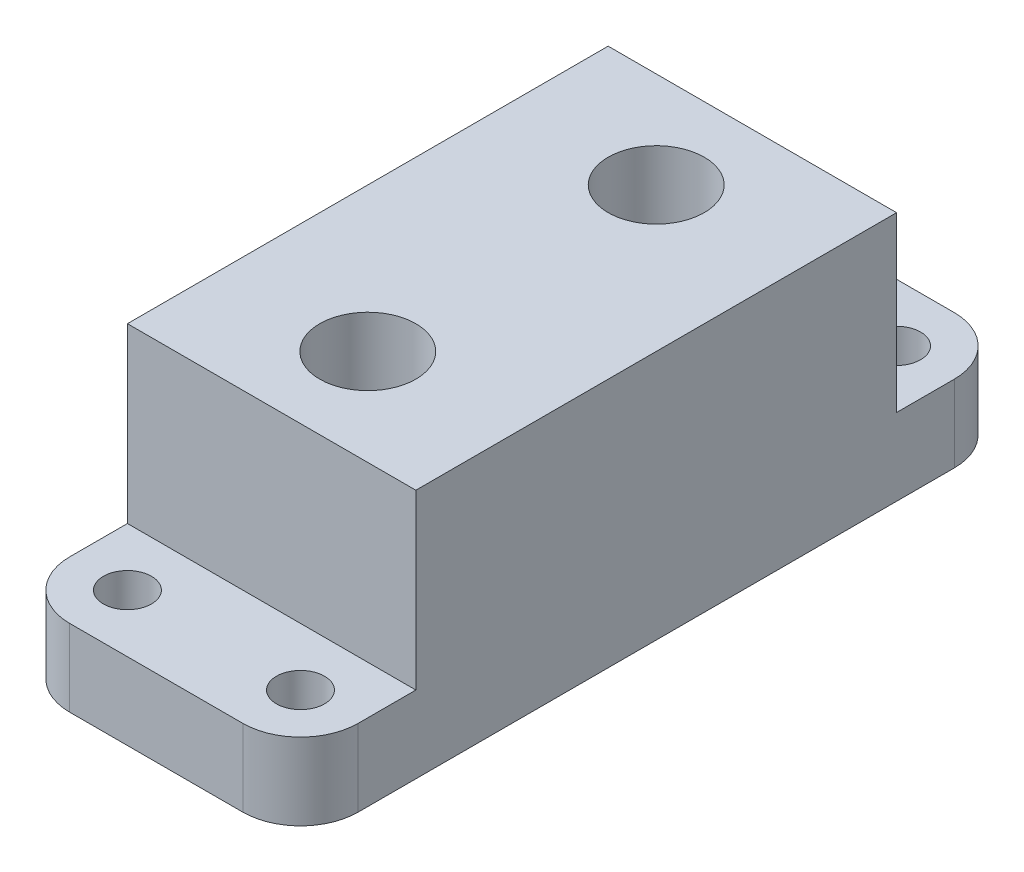
SolidWorks part; units mm, degrees
ref_plane "前视基准面" through (0, 0, 0) normal (0, 0, 1) x (1, 0, 0)
ref_plane "上视基准面" through (0, 0, 0) normal (0, 1, 0) x (1, 0, 0)
ref_plane "右视基准面" through (0, 0, 0) normal (1, 0, 0) x (0, 0, -1)
other "Configuration Table"
sketch "草图1" plane through (0, 0, 0) normal (0, 1, 0) x (1, 0, 0)
  line L1 (-32.5, 12.5) -> (32.5, 12.5)
  line L2 (-32.5, 12.5) -> (-32.5, -12.5)
  line L3 (-32.5, -12.5) -> (32.5, -12.5)
  line L4 (32.5, 12.5) -> (32.5, -12.5)
  line L5 (0, -12.5) -> (0, 12.5) construction
  line L6 (-32.5, 0) -> (32.5, 0) construction
  point P0 (0, 0)
  dimension "D1" = 25
  dimension "D2" = 65
extrude "凸台-拉伸1" add sketch "草图1" along normal blind 4
sketch "草图2" plane through (0, 4, 0) normal (0, 1, 0) x (1, 0, 0)
  line L0 (-32.5, -12.5) -> (32.5, -12.5) construction
  line L1 (-7.5, 12.5) -> (7.5, 12.5)
  line L2 (-7.5, 12.5) -> (-7.5, -12.5)
  line L3 (-7.5, -12.5) -> (7.5, -12.5)
  line L4 (7.5, 12.5) -> (7.5, -12.5)
  line L5 (0, -12.5) -> (0, 12.5) construction
  line L6 (-7.5, 0) -> (7.5, 0) construction
  point P0 (0, 0)
  dimension "D1" = 15
extrude "凸台-拉伸2" add sketch "草图2" along normal blind 13
sketch "草图3" plane through (0, 0, 0) normal (0, -1, 0) x (1, 0, 0)
  line L0 (0, 12.5) -> (0, -12.5) construction
  line L1 (-32.5, 12.5) -> (32.5, 12.5) construction
  line L2 (32.5, -12.5) -> (-32.5, -12.5) construction
  line L3 (-32.5, 0) -> (32.5, 0) construction
  line L4 (-32.5, -12.5) -> (-32.5, 12.5) construction
  line L5 (32.5, 12.5) -> (32.5, -12.5) construction
  circle A0 centre (0, -7.5) radius 2.5
  circle A1 centre (0, 7.5) radius 2.5
  circle A2 centre (-22, 0) radius 4
  circle A3 centre (22, 0) radius 4
  dimension "D1" = 5
  dimension "D3" = 8
  dimension "D2" = 5
  dimension "D4" = 22
extrude "切除-拉伸1" cut sketch "草图3" against normal through all
sketch "草图5" plane through (0, 0, 12.5) normal (0, 0, 1) x (1, 0, 0)
  line L0 (7.5, 17) -> (7.5, 4) construction
  line L1 (-7.5, 4) -> (7.5, 4)
  line L2 (-7.5, 4) -> (-7.5, 8)
  line L3 (-7.5, 8) -> (7.5, 8)
  line L4 (7.5, 4) -> (7.5, 8)
  dimension "D1" = 4
extrude "凸台-拉伸3" add sketch "草图5" along normal blind 6
sketch "草图6" plane through (0, 4, 0) normal (0, -1, 0) x (1, 0, 0)
  line L0 (0, 18.5) -> (0, 12.5) construction
  line L1 (-7.5, 18.5) -> (7.5, 18.5) construction
  line L2 (-32.5, 12.5) -> (32.5, 12.5) construction
  line L3 (-7.5, 18.5) -> (-7.5, 12.5) construction
  circle A0 centre (-4.5, 15.5) radius 1.25
  circle A1 centre (4.5, 15.5) radius 1.25
  point P8 (0, 0)
  point P11 (-7.5, 15.5)
  dimension "D1" = 2.5
  dimension "D2" = 3
extrude "切除-拉伸3" cut sketch "草图6" against normal through all
ref_plane "基准面2" through (0, 0, 0) normal (0, 0, 1) x (1, 0, 0)
mirror "镜向2" about plane through (0, 0, 0) normal (0, 0, 1) of "凸台-拉伸3", "切除-拉伸3"
fillet "圆角2" radius 3 4 edges at (-7.5, 6, -18.5) (7.5, 6, -18.5) (-7.5, 6, 18.5) (7.5, 6, 18.5)
sketch "草图7" plane through (0, 0, -12.5) normal (0, 0, -1) x (-1, 0, 0)
  line L6 (32.5, 4) -> (7.5, 4)
  line L7 (7.5, 4) -> (-7.5, 4)
  line L8 (-7.5, 4) -> (-32.5, 4)
  line L9 (-32.5, 4) -> (-32.5, 0)
  line L10 (-32.5, 0) -> (32.5, 0)
  line L11 (32.5, 0) -> (32.5, 4)
  line L12 (32.5, 4) -> (7.5, 4)
  line L13 (7.5, 4) -> (-7.5, 4)
  line L14 (-7.5, 4) -> (-32.5, 4)
  line L15 (-32.5, 4) -> (-32.5, 0)
  line L16 (-32.5, 0) -> (32.5, 0)
  line L17 (32.5, 0) -> (32.5, 4)
  dimension "D1" = 0
extrude "切除-拉伸4" cut sketch "草图7" against normal through all
